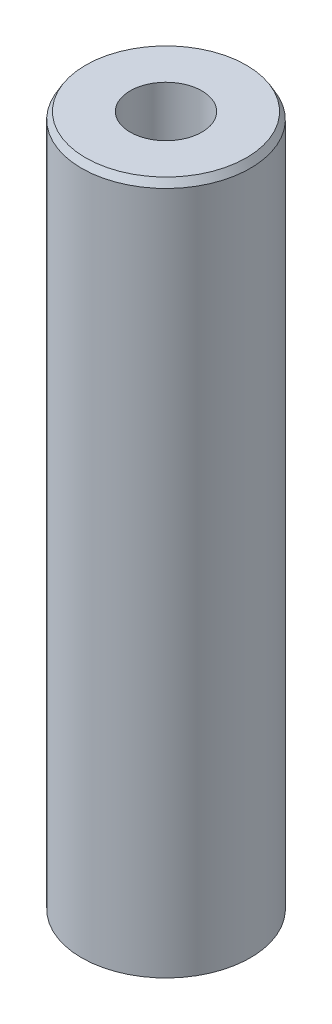
SolidWorks part; units mm, degrees
ref_plane "Front Plane" through (0, 0, 0) normal (0, 0, 1) x (1, 0, 0)
ref_plane "Top Plane" through (0, 0, 0) normal (0, 1, 0) x (1, 0, 0)
ref_plane "Right Plane" through (0, 0, 0) normal (1, 0, 0) x (0, 0, -1)
sketch "Sketch1" plane through (0, 0, 0) normal (0, 1, 0) x (1, 0, 0)
  circle A0 centre (0, 0) radius 57.5
  dimension "SHAFT_OD" = 115
extrude "Boss-Extrude1" add sketch "Sketch1" along normal blind 473.3903
sketch "Sketch2" plane through (0, 0, 0) normal (0, 1, 0) x (1, 0, 0)
  circle A0 centre (0, 0) radius 24.423
  dimension "BORE_D" = 48.846
extrude "Cut-Extrude1" cut sketch "Sketch2" along normal through all
chamfer "Chamfer1" distance 4.7892 angle 30 2 edges at (0, 473.3903, 57.5) (0, 0, 57.5) first distance on face at (0, 473.3903, 57.5) first distance on face at (0, 0, 24.423)
